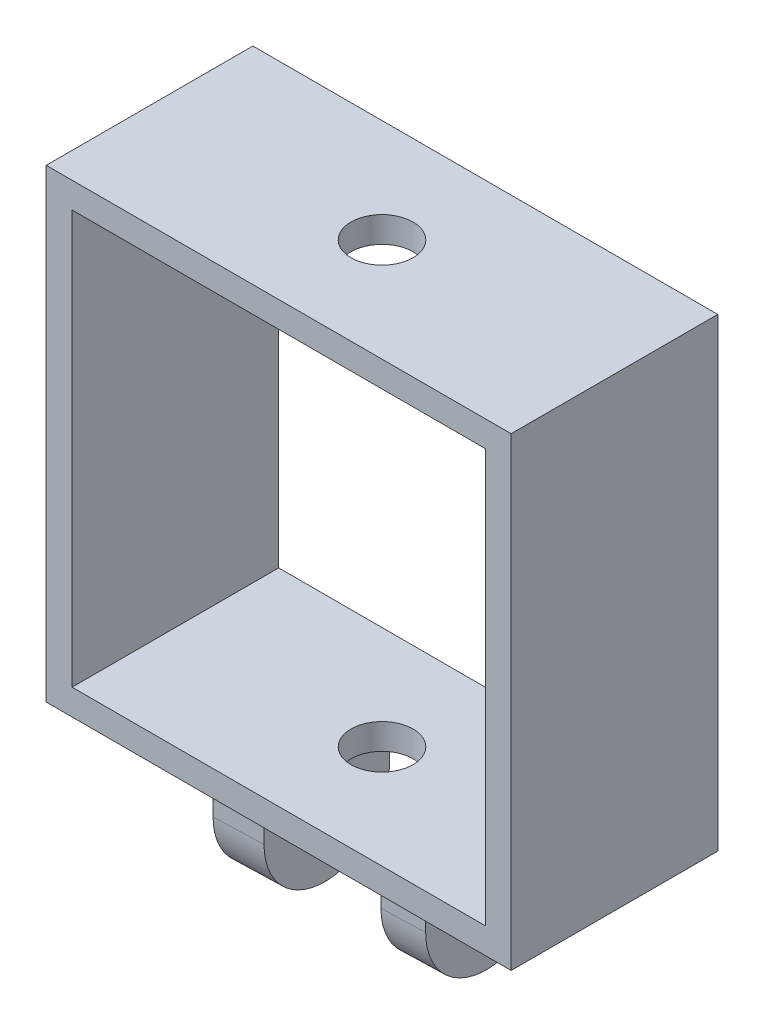
SolidWorks part; units mm, degrees
material "2024 合金"
ref_plane "前视基准面" through (0, 0, 0) normal (0, 0, 1) x (1, 0, 0)
ref_plane "上视基准面" through (0, 0, 0) normal (0, 1, 0) x (1, 0, 0)
ref_plane "右视基准面" through (0, 0, 0) normal (1, 0, 0) x (0, 0, -1)
sketch "草图1" plane through (0, 0, 0) normal (0, 0, 1) x (1, 0, 0)
  line L1 (-45, -45) -> (45, -45)
  line L2 (-45, -45) -> (-45, 45)
  line L3 (-45, 45) -> (45, 45)
  line L4 (45, -45) -> (45, 45)
  line L5 (-45, -45) -> (45, 45) construction
  line L6 (-45, 45) -> (45, -45) construction
  line L7 (-40, -40) -> (40, -40)
  line L8 (-40, -40) -> (-40, 40)
  line L9 (-40, 40) -> (40, 40)
  line L10 (40, -40) -> (40, 40)
  line L11 (-40, -40) -> (40, 40) construction
  line L12 (-40, 40) -> (40, -40) construction
  point P0 (0, 0)
  point P7 (0, 0)
  dimension "D1" = 90
  dimension "D2" = 90
  dimension "D3" = 80
  dimension "D4" = 80
extrude "凸台-拉伸1" add sketch "草图1" along normal blind 40
sketch "草图3" plane through (0, 45, 0) normal (0, 1, 0) x (1, 0, 0)
  line L0 (0, 0) -> (0, -20) construction
  line L1 (45, 0) -> (-45, 0) construction
  circle A0 centre (0, -20) radius 6
  dimension "D2" = 12
  dimension "D1" = 20
extrude "切除-拉伸2" cut sketch "草图3" against normal through all
sketch "草图4" plane through (1.5966, -1.9977, 74.2418) normal (0.9996, 0, -0.0294) x (-0.0294, 0, -0.9996)
  line L0 (41.7652, -43.0023) -> (41.7652, -53.0023)
  line L1 (66.7652, -53.0023) -> (66.7652, -43.0023)
  line L2 (66.7652, -43.0023) -> (41.7652, -43.0023)
  line L3 (54.2652, -42.5) -> (54.2652, -53.0023) construction
  line L4 (35.5979, -43.0023) -> (75.5806, -43.0023) construction
  arc A0 (41.7652, -53.0023) -> (66.7652, -53.0023) centre (54.2652, -53.0023) ccw
  circle A1 centre (54.2652, -53.0023) radius 4
  dimension "D3" = 8
  dimension "D1" = 25
  dimension "D2" = 10
extrude "凸台-拉伸2" add sketch "草图4" along normal blind 20 and the other way blind 20
sketch "草图5" plane through (0.2204, 0, 7.4881) normal (-0.0294, 0, -0.9996) x (-0.9996, 0, 0.0294)
  line L0 (0, 0) -> (0, -60) construction
  line L1 (11, -45) -> (-11, -45)
  line L2 (11, -45) -> (11, -75)
  line L3 (11, -75) -> (-11, -75)
  line L4 (-11, -45) -> (-11, -75)
  line L5 (11, -45) -> (-11, -75) construction
  line L6 (11, -75) -> (-11, -45) construction
  line L7 (44.9805, -45) -> (-44.9805, -45) construction
  point P0 (0, -60)
  dimension "D1" = 22
  dimension "D2" = 30
extrude "切除-拉伸3" cut sketch "草图5" against normal through all
